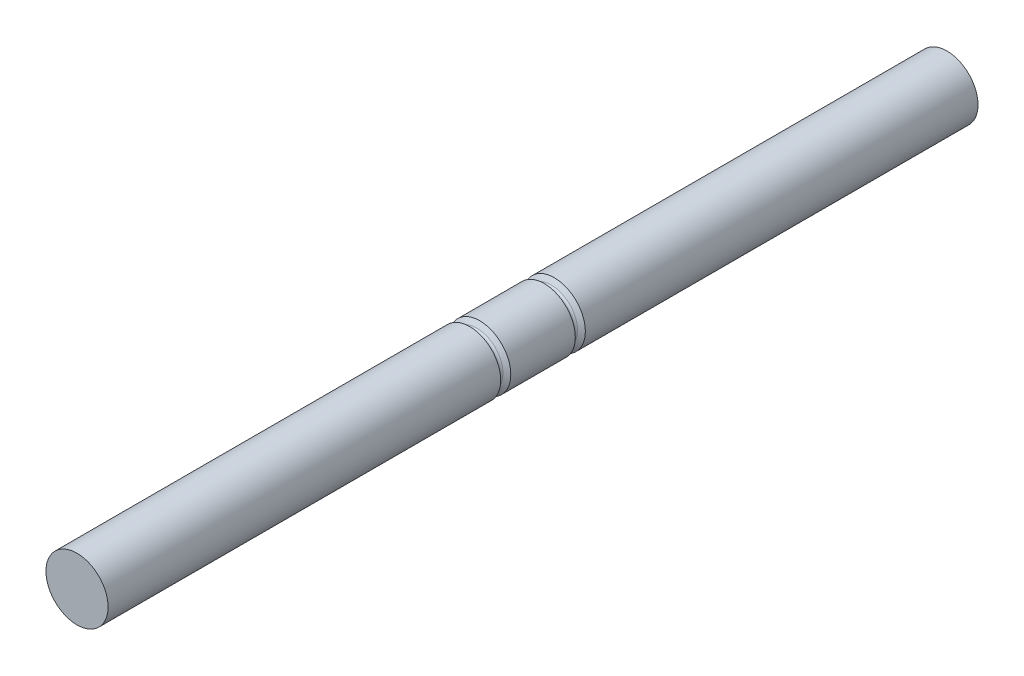
SolidWorks part; units mm, degrees
material "Plain Carbon Steel"
ref_plane "Front Plane" through (0, 0, 0) normal (0, 0, 1) x (1, 0, 0)
ref_plane "Top Plane" through (0, 0, 0) normal (0, 1, 0) x (1, 0, 0)
ref_plane "Right Plane" through (0, 0, 0) normal (1, 0, 0) x (0, 0, -1)
sketch "Sketch1" plane through (0, 0, 0) normal (0, 0, 1) x (1, 0, 0)
  circle A0 centre (0, 0) radius 1.5875
  dimension "D1" = 3.175
extrude "Body" add sketch "Sketch1" against normal blind 44.45
sketch "Sketch2" plane through (0, 0, 0) normal (0, 1, 0) x (1, 0, 0)
  line L0 (0, 22.225) -> (-8.5875, 22.225) construction
  line L1 (-2.2429, 19.685) -> (-2.2429, 20.955)
  line L2 (-2.2429, 20.955) -> (-1.3335, 20.43)
  line L3 (-2.2429, 23.495) -> (-1.3335, 24.02)
  line L4 (-1.3335, 20.21) -> (-2.2429, 19.685)
  line L5 (-1.3335, 24.24) -> (-2.2429, 24.765)
  line L6 (-2.2429, 24.765) -> (-2.2429, 23.495)
  line L9 (0, 0) -> (0, 44.45) construction
  line L10 (1.5875, 44.45) -> (-1.5875, 44.45) construction
  line L11 (1.5875, 44.45) -> (-1.5875, 44.45) construction
  arc A0 (-1.3335, 20.21) -> (-1.3335, 20.43) centre (-1.397, 20.32) ccw
  arc A1 (-1.3335, 24.24) -> (-1.3335, 24.02) centre (-1.397, 24.13) cw
  point P15 (0, 22.225)
  dimension "D4" = 0.254
  dimension "D3" = 1.27
  dimension "D1" = 60
  dimension "D2" = 60
  dimension "D5" = 1.397
  dimension "D6" = 1.905
revolve "WireSlots" cut sketch "Sketch2" angle 360 about L9
